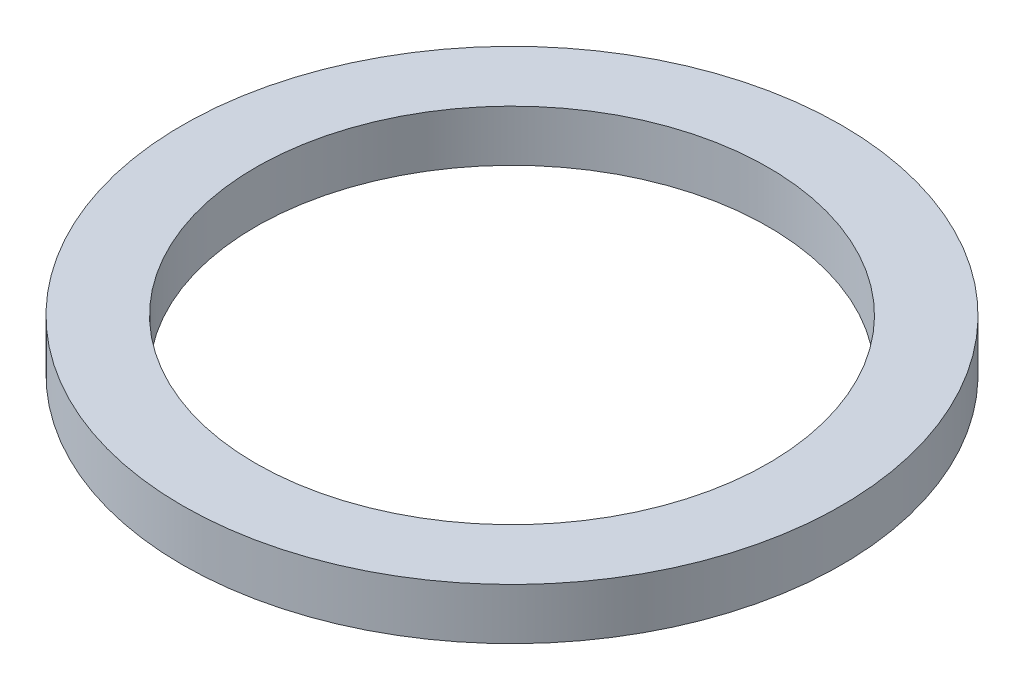
SolidWorks part; units mm, degrees
ref_plane "Front Plane" through (0, 0, 0) normal (0, 0, 1) x (1, 0, 0)
ref_plane "Top Plane" through (0, 0, 0) normal (0, 1, 0) x (1, 0, 0)
ref_plane "Right Plane" through (0, 0, 0) normal (1, 0, 0) x (0, 0, -1)
sketch "Sketch1" plane through (0, 0, 0) normal (0, 1, 0) x (1, 0, 0)
  circle A0 centre (0, 0) radius 45
  dimension "FLANGE_OD" = 90
extrude "Boss-Extrude1" add sketch "Sketch1" along normal blind 7
sketch "Sketch2" plane through (0, 0, 0) normal (0, 1, 0) x (1, 0, 0)
  circle A0 centre (0, 0) radius 35
  dimension "BORE_D" = 70
extrude "Cut-Extrude1" cut sketch "Sketch2" along normal through all
sketch "Sketch3" plane through (0, 7, 0) normal (0, 1, 0) x (1, 0, 0)
  circle A0 centre (0, 0) radius 20.1183 construction
  circle A1 centre (-20.1183, 0) radius 1.5076
  dimension "BOLT_D" = 3.0152
  dimension "BOLT_PCD" = 40.2365
extrude "Cut-Extrude2" cut sketch "Sketch3" against normal blind 5.2873 rebuild error yes
pattern_circular "CirPattern1" count 6 over 360 rebuild error yes
